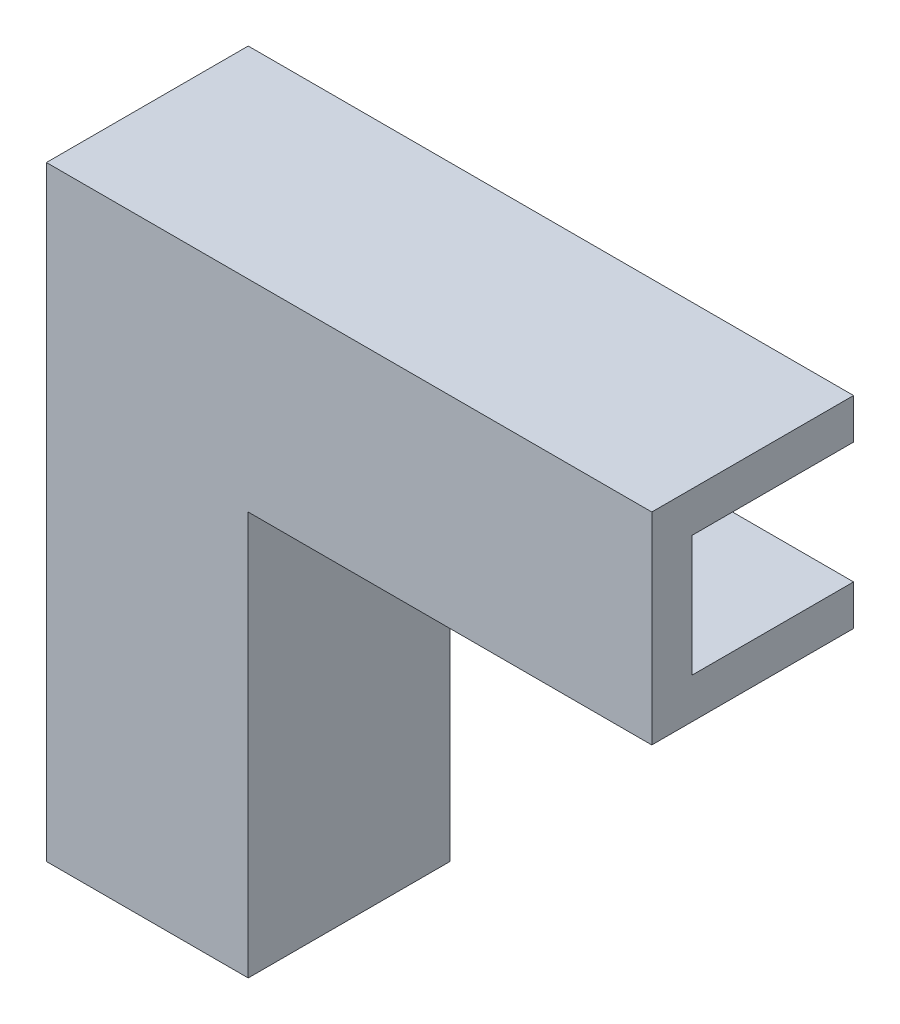
SolidWorks part; units mm, degrees
ref_plane "Plan de face" through (0, 0, 0) normal (0, 0, 1) x (1, 0, 0)
ref_plane "Plan de dessus" through (0, 0, 0) normal (0, 1, 0) x (1, 0, 0)
ref_plane "Plan de droite" through (0, 0, 0) normal (1, 0, 0) x (0, 0, -1)
sketch "Esquisse1" plane through (0, 0, 0) normal (0, 0, 1) x (1, 0, 0)
  line L0 (-1.3179, -12.6336) -> (-1.3179, -2.6336)
  line L1 (-6.3179, 2.3664) -> (8.6821, 2.3664)
  line L2 (-6.3179, 2.3664) -> (-6.3179, -12.6336)
  line L3 (-6.3179, -12.6336) -> (-1.3179, -12.6336)
  line L4 (8.6821, 2.3664) -> (8.6821, -2.6336)
  line L5 (-1.3179, -2.6336) -> (8.6821, -2.6336)
  dimension "D1" = 15
  dimension "D2" = 15
  dimension "D3" = 5
  dimension "D4" = 5
extrude "Boss.-Extru.1" add sketch "Esquisse1" along normal blind 5
sketch "Esquisse2" plane through (0, -12.6336, 0) normal (0, -1, 0) x (1, 0, 0)
  line L0 (-6.3179, 0) -> (-1.3179, 0) construction
  line L1 (-5.3179, 0) -> (-2.3179, 0)
  line L2 (-5.3179, 0) -> (-5.3179, 4)
  line L3 (-5.3179, 4) -> (-2.3179, 4)
  line L4 (-2.3179, 0) -> (-2.3179, 4)
  line L5 (-6.3179, 5) -> (-6.3179, 0) construction
  line L6 (-1.3179, 5) -> (-1.3179, 0) construction
  line L7 (-6.3179, 5) -> (-1.3179, 5) construction
  dimension "D1" = 1
  dimension "D2" = 1
  dimension "D3" = 1
extrude "Enlèv. mat.-Extru.1" cut sketch "Esquisse2" against normal blind 14
sketch "Esquisse3" plane through (8.6821, 0, 0) normal (1, 0, 0) x (0, 0, -1)
  line L0 (0, -2.6336) -> (0, 2.3664) construction
  line L1 (0, 1.3664) -> (-4, 1.3664)
  line L2 (0, 1.3664) -> (0, -1.6336)
  line L3 (0, -1.6336) -> (-4, -1.6336)
  line L4 (-4, 1.3664) -> (-4, -1.6336)
  line L5 (-5, -2.6336) -> (0, -2.6336) construction
  line L6 (-5, 2.3664) -> (0, 2.3664) construction
  line L7 (-5, -2.6336) -> (-5, 2.3664) construction
  dimension "D1" = 1
  dimension "D2" = 1
  dimension "D3" = 1
extrude "Enlèv. mat.-Extru.2" cut sketch "Esquisse3" against normal blind 14
